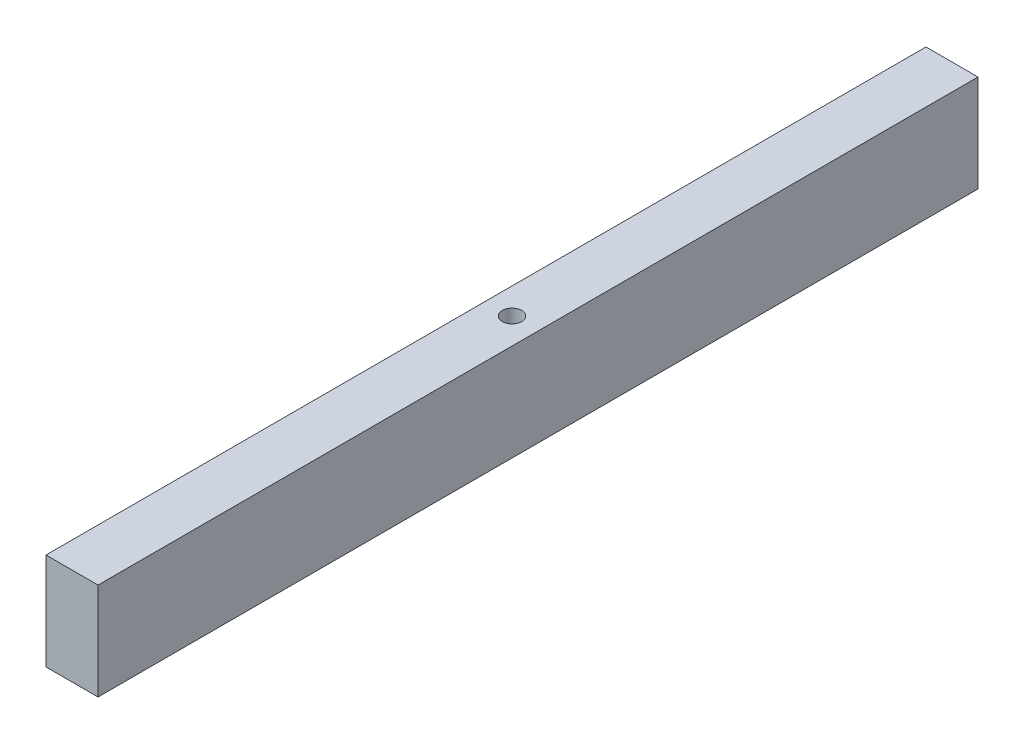
SolidWorks part; units mm, degrees
material "Gray Cast Iron"
ref_plane "Front Plane" through (0, 0, 0) normal (0, 0, 1) x (1, 0, 0)
ref_plane "Top Plane" through (0, 0, 0) normal (0, 1, 0) x (1, 0, 0)
ref_plane "Right Plane" through (0, 0, 0) normal (1, 0, 0) x (0, 0, -1)
sketch "Sketch1" plane through (0, 0, 0) normal (0, 0, 1) x (1, 0, 0)
  line L0 (-11, 0) -> (11, 0)
  line L1 (11, 0) -> (11, 41)
  line L2 (11, 41) -> (-11, 41)
  line L3 (-11, 41) -> (-11, 0)
extrude "Boss-Extrude1" add sketch "Sketch1" along normal mid plane 372
sketch "Sketch2" plane through (0, 0, 0) normal (0, 1, 0) x (1, 0, 0)
  circle A0 centre (0, 0) radius 4.1
  dimension "D1" = 8.2
extrude "Cut-Extrude1" cut sketch "Sketch2" against normal mid plane 92
